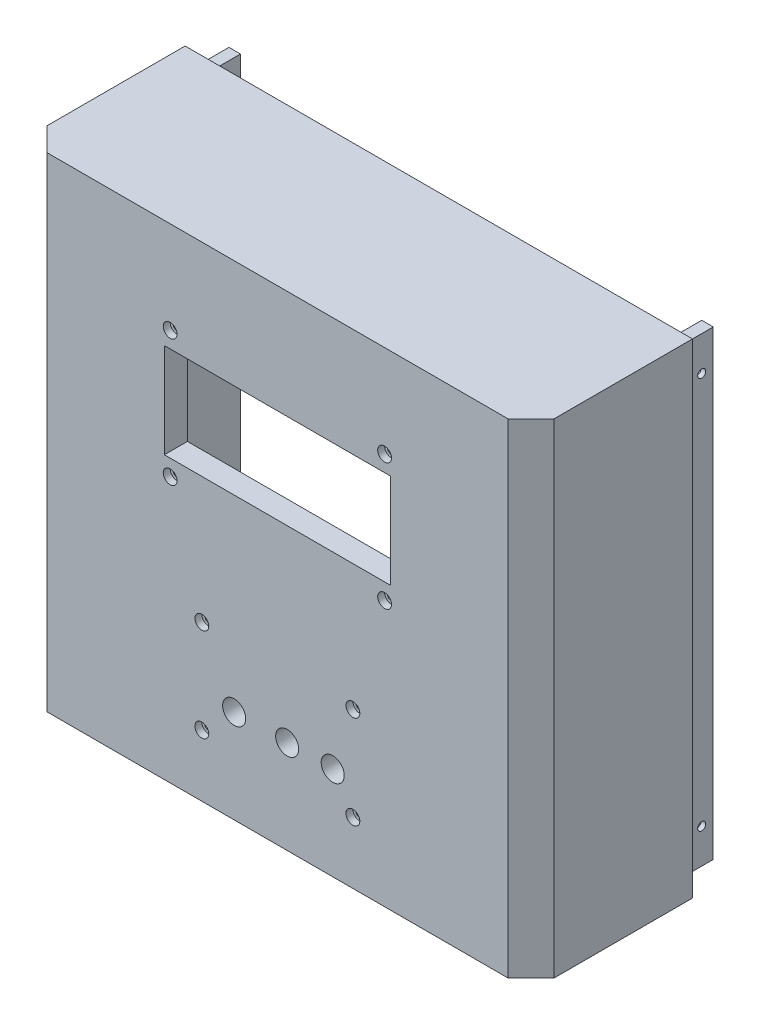
SolidWorks part; units mm, degrees
ref_plane "Płaszczyzna przednia" through (0, 0, 0) normal (0, 0, 1) x (1, 0, 0)
ref_plane "Płaszczyzna górna" through (0, 0, 0) normal (0, 1, 0) x (1, 0, 0)
ref_plane "Płaszczyzna prawa" through (0, 0, 0) normal (1, 0, 0) x (0, 0, -1)
sketch "Sketch1" plane through (0, 0, 0) normal (0, 1, 0) x (1, 0, 0)
  line L0 (0, 0) -> (100, 0)
  line L1 (100, 0) -> (110, 10)
  line L2 (110, 10) -> (110, 70)
  line L3 (110, 70) -> (100, 70)
  line L4 (100, 70) -> (100, 10)
  line L6 (100, 10) -> (0, 10)
  line L7 (0, 10) -> (0, 0)
  dimension "D1" = 10
  dimension "D2" = 10
  dimension "D3" = 60
  dimension "D4" = 10
  dimension "D5" = 10
  dimension "D6" = 100
extrude "Boss-Extrude1" add sketch "Sketch1" along normal blind 200
mirror "Mirror1" about plane through (0, 0, 0) normal (1, 0, 0) of "Boss-Extrude1"
sketch "Sketch2" plane through (0, 0, 0) normal (1, 0, 0) x (0, 0, -1)
  line L0 (48, 0) -> (48, 95.5652) construction
  line L2 (0, 180) -> (91.2882, 180) construction
  line L4 (10, 200) -> (10, 0) construction
  line L7 (10, 200) -> (70, 200) construction
  line L8 (88.1265, 71) -> (-11.2927, 71) construction
  circle A0 centre (29.5, 103) radius 1.75
  circle A1 centre (38.5, 180) radius 1.75
  circle A2 centre (20.5, 180) radius 1.75
  dimension "D3" = 32
  dimension "D7" = 3.5
  dimension "D1" = 38
  dimension "D2" = 18.5
  dimension "D4" = 77
  dimension "D5" = 9.5
  dimension "D6" = 18
  dimension "D8" = 129
sketch "Sketch6" plane through (0, 0, 0) normal (0, 1, 0) x (1, 0, 0)
  line L0 (110, 70) -> (-110, 70)
  line L1 (-110, 70) -> (-110, 10)
  line L2 (-110, 10) -> (-100, 0)
  line L3 (-100, 0) -> (100, 0)
  line L4 (100, 0) -> (110, 10)
  line L5 (110, 10) -> (110, 70)
extrude "Boss-Extrude2" add sketch "Sketch6" against normal blind 5
extrude "Boss-Extrude3" add sketch "Sketch6<2>" along normal blind 5 from surface starting at face at (0, 200, -32)
sketch "Sketch6<2>" plane through (0, 0, 0) normal (0, 1, 0) x (1, 0, 0) same geometry as "Sketch6"
sketch "Sketch12" plane through (0, 0, 0) normal (0, 0, 1) x (1, 0, 0)
  line L1 (100, 200) -> (105, 200)
  line L2 (100, 200) -> (100, 0)
  line L3 (100, 0) -> (105, 0)
  line L4 (105, 200) -> (105, 0)
  line L5 (-100, 0) -> (-105, 0)
  line L6 (-100, 0) -> (-100, 200)
  line L7 (-100, 200) -> (-105, 200)
  line L8 (-105, 0) -> (-105, 200)
  dimension "D1" = 5
  dimension "D2" = 5
extrude "Boss-Extrude5" add sketch "Sketch12" against normal blind 14 from surface starting at face at (0, 100, -70)
sketch "Sketch13" plane through (0, 0, 0) normal (0, 0, 1) x (1, 0, 0)
  line L0 (100, 205) -> (-100, 205) construction
  line L1 (-46.5, 165) -> (46.5, 165) construction
  line L2 (-46.5, 165) -> (-46.5, 110) construction
  line L3 (-46.5, 110) -> (46.5, 110) construction
  line L4 (46.5, 165) -> (46.5, 110) construction
  line L5 (-46.5, 165) -> (46.5, 110) construction
  line L6 (-46.5, 110) -> (46.5, 165) construction
  line L7 (-49, 117) -> (49, 117)
  line L8 (-49, 117) -> (-49, 158)
  line L9 (-49, 158) -> (49, 158)
  line L10 (49, 117) -> (49, 158)
  line L11 (-49, 117) -> (49, 158) construction
  line L12 (-49, 158) -> (49, 117) construction
  line L15 (-32.75, 35.4962) -> (32.75, 35.4962) construction
  line L16 (32.75, 62.2462) -> (-32.75, 62.2462) construction
  line L17 (32.75, 62.2462) -> (32.75, 21.7462) construction
  line L18 (32.75, 21.7462) -> (-32.75, 21.7462) construction
  line L19 (-32.75, 62.2462) -> (-32.75, 21.7462) construction
  line L20 (32.75, 62.2462) -> (-32.75, 21.7462) construction
  line L21 (32.75, 21.7462) -> (-32.75, 62.2462) construction
  line L22 (-36, 18.4962) -> (36, 18.4962) construction
  line L23 (-36, 18.4962) -> (-36, 65.4962) construction
  line L24 (-36, 65.4962) -> (36, 65.4962) construction
  line L25 (36, 18.4962) -> (36, 65.4962) construction
  line L26 (-36, 18.4962) -> (36, 65.4962) construction
  line L27 (-36, 65.4962) -> (36, 18.4962) construction
  circle A0 centre (-46.5, 165) radius 1.75
  circle A1 centre (46.5, 165) radius 1.75
  circle A2 centre (46.5, 110) radius 1.75
  circle A3 centre (-46.5, 110) radius 1.75
  circle A4 centre (32.75, 62.2462) radius 1.75
  circle A5 centre (-32.75, 62.2462) radius 1.75
  circle A6 centre (32.75, 21.7462) radius 1.75
  circle A7 centre (-32.75, 21.7462) radius 1.75
  circle A8 centre (24, 35.4962) radius 5
  circle A10 centre (-18.75, 35.4962) radius 5
  circle A11 centre (4.25, 35.4962) radius 5
  point P0 (0, 137.5)
  point P5 (0, 137.5)
  point P17 (0, 0)
  point P22 (0, 0)
  dimension "D5" = 3.5
  dimension "D9" = 3.5
  dimension "D10" = 3.5
  dimension "D11" = 3.5
  dimension "D12" = 3.5
  dimension "D13" = 10
  dimension "D17" = 37
  dimension "D19" = 10
  dimension "D20" = 10
  dimension "D1" = 93
  dimension "D2" = 98
  dimension "D3" = 55
  dimension "D4" = 41
  dimension "D6" = 40
  dimension "D7" = 65.5
  dimension "D8" = 40.5
  dimension "D14" = 72
  dimension "D15" = 47
  dimension "D16" = 14
  dimension "D18" = 12
  dimension "D21" = 30
extrude "Cut-Extrude7" cut sketch "Sketch13" against normal through all both and the other way through all
sketch "Sketch15" plane through (0, 0, 0) normal (0, 0, 1) x (1, 0, 0)
  circle A0 centre (-46.5, 165) radius 3
  circle A1 centre (46.5, 165) radius 3
  circle A2 centre (46.5, 110) radius 3
  circle A3 centre (-46.5, 110) radius 3
  dimension "D1" = 6
extrude "Cut-Extrude8" cut sketch "Sketch15" against normal blind 3 from surface starting at face at (44.75, 165, 0)
sketch "Sketch16" plane through (0, 0, 0) normal (1, 0, 0) x (0, 0, -1)
  line L0 (79, 204.548) -> (79, -4.9329) construction
  line L2 (10, 205) -> (70, 205) construction
  line L3 (70, -5) -> (10, -5) construction
  line L4 (70, 200) -> (70, 0) construction
  circle A0 centre (79, 185) radius 1.75
  circle A1 centre (79, 15) radius 1.75
  dimension "D2" = 3.5
  dimension "D1" = 9
  dimension "D3" = 20
  dimension "D4" = 20
extrude "Cut-Extrude9" cut sketch "Sketch16" against normal through all both and the other way through all
sketch "Sketch17" plane through (0, 0, 0) normal (1, 0, 0) x (0, 0, -1)
  line L1 (75.5359, 185) -> (77.2679, 182)
  line L2 (77.2679, 182) -> (80.7321, 182)
  line L3 (80.7321, 182) -> (82.4641, 185)
  line L4 (82.4641, 185) -> (80.7321, 188)
  line L5 (80.7321, 188) -> (77.2679, 188)
  line L6 (77.2679, 188) -> (75.5359, 185)
  line L7 (75.6907, 13.9761) -> (78.2321, 11.6221)
  line L8 (78.2321, 11.6221) -> (81.5414, 12.646)
  line L9 (81.5414, 12.646) -> (82.3093, 16.0239)
  line L10 (82.3093, 16.0239) -> (79.7679, 18.3779)
  line L11 (79.7679, 18.3779) -> (76.4586, 17.354)
  line L12 (76.4586, 17.354) -> (75.6907, 13.9761)
  circle A0 centre (79, 185) radius 3 construction
  circle A1 centre (79, 15) radius 3 construction
  point P10 (76.0746, 15.665)
  dimension "D1" = 6
  dimension "D2" = 6
extrude "Cut-Extrude10" cut sketch "Sketch17" against normal blind 3 from surface starting at face at (-100, 185, -80.75)
extrude "Cut-Extrude11" cut sketch "Sketch17<2>" along normal blind 3 from surface starting at face at (100, 185, -80.75)
sketch "Sketch17<2>" plane through (0, 0, 0) normal (1, 0, 0) x (0, 0, -1) same geometry as "Sketch17"
sketch "Sketch18" plane through (0, 0, 0) normal (0, 0, 1) x (1, 0, 0)
  circle A0 centre (32.75, 62.2462) radius 3
  circle A1 centre (-32.75, 62.2462) radius 3
  circle A2 centre (-32.75, 21.7462) radius 3
  circle A3 centre (32.75, 21.7462) radius 3
  dimension "D1" = 6
extrude "Cut-Extrude12" cut sketch "Sketch18" against normal blind 3 from surface starting at face at (-49.5, 110, 0)
